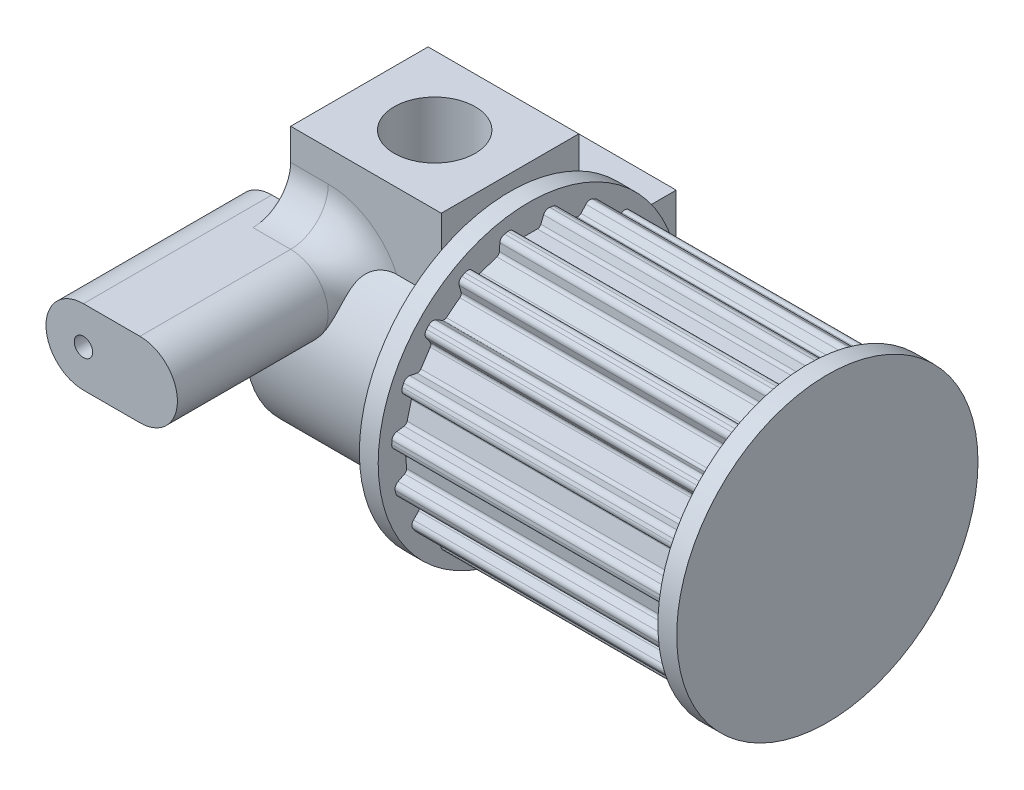
SolidWorks part; units mm, degrees
material "PLA Black"
ref_plane "Front" through (0, 0, 0) normal (0, 0, 1) x (1, 0, 0)
ref_plane "Top" through (0, 0, 0) normal (0, 1, 0) x (1, 0, 0)
ref_plane "Right" through (0, 0, 0) normal (1, 0, 0) x (0, 0, -1)
sketch "Sketch1" plane through (0, 0, 0) normal (1, 0, 0) x (0, 0, -1)
  line L0 (1.118, 1) -> (-1.118, 1) construction
  line L1 (-3.65, 4.8249) -> (3.65, 4.8249)
  line L2 (4.8249, 3.65) -> (4.8249, -3.65)
  line L3 (0, 0) -> (11.6334, 0) construction
  line L4 (0, 0) -> (0, 8.6732) construction
  arc A0 (-1.118, 1) -> (1.118, 1) centre (0, 0) ccw construction
  circle A1 centre (0, 0) radius 1.75
  arc A2 (4.8249, -3.65) -> (-3.65, 4.8249) centre (0, 0) cw
  arc A3 (4.8249, 3.65) -> (3.65, 4.8249) centre (0, 0) ccw
  dimension "D1" = 3
  dimension "D3" = 0.25
  dimension "D5" = 6.05
  dimension "D2" = 1
  dimension "D4" = 7.3
extrude "Boss-Extrude1" add sketch "Sketch1" along normal mid plane 8
sketch "Sketch2" plane through (0, 4.8249, 0) normal (0, 1, 0) x (1, 0, 0)
  circle A0 centre (0, 0) radius 2.15
  dimension "D1" = 4.3
extrude "Cut-Extrude1" cut sketch "Sketch2" against normal blind 5
sketch "Sketch7" plane through (4, 0, 0) normal (1, 0, 0) x (0, 0, -1)
  circle A0 centre (0, 0) radius 1.75 construction
  circle A1 centre (0, 0) radius 7.3
  circle A2 centre (0, 0) radius 1.75
  dimension "D1" = 14.6
extrude "Boss-Extrude5" add sketch "Sketch7" along normal blind 15.85
sketch "Sketch8" plane through (19.85, 0, 0) normal (1, 0, 0) x (0, 0, -1)
  line L0 (-0.4541, 6.5499) -> (0.4528, 6.5499)
  line L1 (0.6374, 6.6734) -> (0.7865, 7.0333)
  line L2 (-0.6389, 6.6734) -> (-0.788, 7.0333)
  line L6 (0, 9.2013) -> (0, 0) construction
  arc A0 (0.4528, 6.5499) -> (0.6374, 6.6734) centre (0.4526, 6.7499) ccw
  arc A1 (-0.4541, 6.5499) -> (-0.6389, 6.6734) centre (-0.4541, 6.7499) cw
  arc A2 (0.7865, 7.0333) -> (1.1093, 7.2152) centre (1.0638, 6.9187) cw
  arc A3 (-0.788, 7.0333) -> (-1.1108, 7.215) centre (-1.0652, 6.9185) ccw
  circle A4 centre (0, 0) radius 7.3 construction
  arc A5 (-1.1108, 7.215) -> (1.1093, 7.2152) centre (0, 0) cw
  point P3 (-0.0007, 6.5499)
  point P15 (0, 9.84)
extrude "Cut-Extrude3" cut sketch "Sketch8" against normal up to surface (15.85 mm away) up to face at (4, 0, -7.3)
pattern_circular "CirPattern1" count 19 over 360 about axis through (19.85, 0, 0) along (-1, 0, 0) of "Cut-Extrude3"
sketch "Sketch9" plane through (19.85, 0, 0) normal (1, 0, 0) x (0, 0, -1)
  circle A0 centre (0, 0) radius 8
  dimension "D1" = 16
extrude "Boss-Extrude6" add sketch "Sketch9" along normal blind 1
sketch "Sketch10" plane through (4, 0, 0) normal (-1, 0, 0) x (0, 0, 1)
  circle A0 centre (0, 0) radius 8
  circle A1 centre (0, 0) radius 8 construction
extrude "Boss-Extrude7" add sketch "Sketch10" against normal blind 1
sketch "Sketch3" plane through (0, 0, -4.8249) normal (0, 0, -1) x (-1, 0, 0)
  circle A0 centre (0, 0) radius 2.15
  dimension "D1" = 4.3
extrude "Cut-Extrude2" cut sketch "Sketch3" against normal blind 5
sketch "Sketch4" plane through (0, 4.8249, 0) normal (0, 1, 0) x (1, 0, 0)
  line L0 (4, 3.65) -> (-4, 3.65) construction
  line L2 (4, -3.65) -> (-4, -3.65) construction
  line L3 (-4, 3.65) -> (-4, -3.65) construction
  line L4 (4, 3.65) -> (-4, 3.65)
  line L5 (4, 3.65) -> (4, -3.65)
  line L6 (4, -3.65) -> (-4, -3.65)
  line L7 (-4, 3.65) -> (-4, -3.65)
  line L8 (4, 7.3) -> (4, -7.3) construction
  circle A0 centre (0, 0) radius 2.15 construction
  circle A1 centre (0, 0) radius 2.15
extrude "Boss-Extrude2" add sketch "Sketch4" along normal blind 4
sketch "Sketch5" plane through (0, 0, -4.8249) normal (0, 0, -1) x (-1, 0, 0)
  line L0 (-4, 3.65) -> (4, 3.65) construction
  line L1 (4, -3.65) -> (4, 3.65) construction
  line L2 (-4, -3.65) -> (4, -3.65) construction
  line L4 (-4, 3.65) -> (4, 3.65)
  line L5 (4, -3.65) -> (4, 3.65)
  line L6 (-4, -3.65) -> (4, -3.65)
  line L7 (-4, -3.65) -> (-4, 3.65)
  line L8 (-4, -7.3) -> (-4, 7.3) construction
  circle A0 centre (0, 0) radius 2.15 construction
  circle A1 centre (0, 0) radius 2.15
extrude "Boss-Extrude3" add sketch "Sketch5" along normal blind 4
ref_axis "Axis1" through (2.15, 0, 0) along (-1, 0, 0)
sketch "Sketch6" plane through (0, 0, 3.65) normal (0, 0, 1) x (1, 0, 0)
  line L0 (-4, 8.8249) -> (-4, 4.8249) construction
  line L2 (-2, 5.1645) -> (-5, 5.1645)
  line L3 (-5, 1.1855) -> (-2, 1.1855)
  line L6 (2.15, 0) -> (-4, 0) construction
  circle A0 centre (-5, 3.175) radius 0.4895
  arc A1 (-5, 5.1645) -> (-5, 1.1855) centre (-5, 3.175) ccw
  arc A2 (-2, 5.1645) -> (-2, 1.1855) centre (-2, 3.175) cw
  dimension "D1" = 0.979
  dimension "D2" = 3.175
  dimension "D3" = 1.5
  dimension "D4" = 1
  dimension "D5" = 3
extrude "Boss-Extrude4" add sketch "Sketch6" along normal blind 10
fillet "Fillet1" radius 2 2 edges at (-1.4188, 5.0777, 3.65) (-3, 5.1645, 3.65)
equation "\"knee_angle\"= 70"
equation "\"ankle_angle\" = 80"
equation "\"hip_angle\" = 40"
equation "\"spring_ankle_parallel_arm_diameter\"= 0.89"
equation "\"spring_ankle_parallel_arm_length\"= 13"
equation "\"spring_ankle_parallel_intern_diameter\"= 6.22"
equation "\"spring_ankle_parallel_angle\"= \"ankle_angle\""
equation "\"spring_ankle_parallel_turns\"= 3"
equation "\"spring_ankle_parallel_pitch\"= \"spring_ankle_parallel_arm_diameter\" * 1.01"
equation "\"spring_ankle_parallel_cutting_distance\"= (1-\"spring_ankle_parallel_angle\" / 360) * \"spring_ankle_parallel_pitch\""
equation "\"spring_ankle_serial_arm_diameter\"= 0.89"
equation "\"spring_ankle_serial_arm_length\"= 10"
equation "\"spring_ankle_serial_intern_diameter\"= 6.22"
equation "\"spring_ankle_serial_angle\"= \"90\""
equation "\"spring_ankle_serial_turns\"= 3"
equation "\"spring_ankle_serial_pitch\"= \"spring_ankle_serial_arm_diameter\" * 1.01"
equation "\"spring_ankle_serial_cutting_distance\"= (1-\"spring_ankle_serial_angle\" / 360) * \"spring_ankle_serial_pitch\""
equation "\"spring_knee_parallel_arm_diameter\"= 0.89"
equation "\"spring_knee_parallel_arm_length\"= 15"
equation "\"spring_knee_parallel_intern_diameter\"= 5.46"
equation "\"spring_knee_parallel_angle\"= -\"knee_angle\" + 90"
equation "\"spring_knee_parallel_turns\"= 3"
equation "\"spring_knee_parallel_pitch\"= \"spring_knee_parallel_arm_diameter\" * 1.01"
equation "\"spring_knee_parallel_cutting_distance\"= (1-(\"spring_knee_parallel_angle\") / 360) * \"spring_knee_parallel_pitch\""
equation "\"spring_knee_serial_arm_diameter\"= 0.89"
equation "\"spring_knee_serial_arm_length\"= 10"
equation "\"spring_knee_serial_intern_diameter\"= 5.46"
equation "\"spring_knee_serial_angle\"= \"90\""
equation "\"spring_knee_serial_turns\"= 3"
equation "\"spring_knee_serial_pitch\"= \"spring_knee_serial_arm_diameter\" * 1.01"
equation "\"spring_knee_serial_cutting_distance\"= (1-\"spring_knee_serial_angle\" / 360) * \"spring_knee_serial_pitch\""
equation "\"D2@Sketch6\" = ( \"spring_knee_serial_intern_diameter\" + \"spring_knee_serial_arm_diameter\" ) / 2"
equation "\"D1@Sketch6\"=\"spring_knee_serial_arm_diameter\"*1.1"
